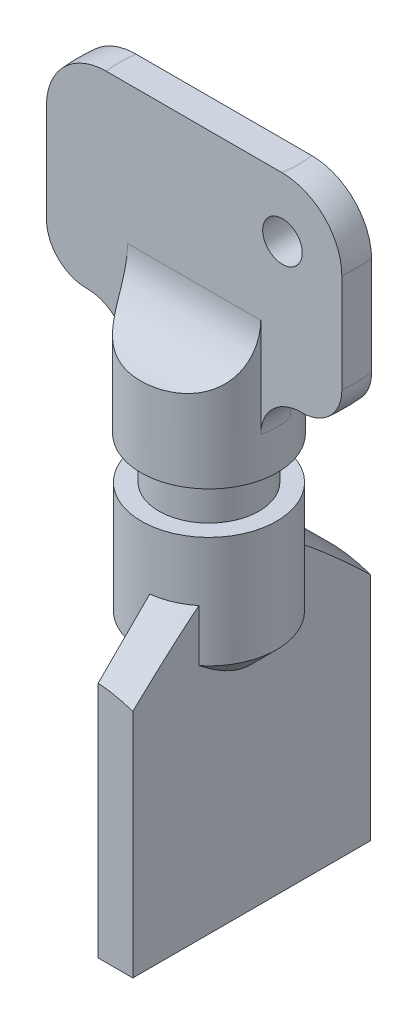
SolidWorks part; units mm, degrees
ref_plane "Front Plane" through (0, 0, 0) normal (0, 0, 1) x (1, 0, 0)
ref_plane "Top Plane" through (0, 0, 0) normal (0, 1, 0) x (1, 0, 0)
ref_plane "Right Plane" through (0, 0, 0) normal (1, 0, 0) x (0, 0, -1)
sketch "Sketch1" plane through (0, 0, 0) normal (0, 0, 1) x (1, 0, 0)
  line L0 (-3.4489, 37.7658) -> (-3.4489, 33.7658)
  line L1 (-3.4489, 33.7658) -> (-2.5348, 33.7658)
  line L2 (-2.5348, 33.7658) -> (-2.5348, 31.625)
  line L3 (-2.5348, 31.625) -> (-3.4177, 31.625)
  line L4 (-3.4177, 31.625) -> (-3.4177, 23)
  line L5 (-3.4177, 23) -> (0, 23)
  line L6 (-3.4489, 37.7658) -> (0, 37.7658)
  line L7 (0, 37.7658) -> (0, 23)
  dimension "D1" = 33.7658
  dimension "D2" = 2.1409
  dimension "D3" = 23
  dimension "D4" = 4
revolve "Revolve1" add sketch "Sketch1" angle 360 about L7
sketch "Sketch2" plane through (0, 37.7658, 0) normal (0, 1, 0) x (1, 0, 0)
  line L1 (-11.4046, 0.75) -> (11.4046, 0.75)
  line L2 (-11.4046, 0.75) -> (-11.4046, -0.75)
  line L3 (-11.4046, -0.75) -> (11.4046, -0.75)
  line L4 (11.4046, 0.75) -> (11.4046, -0.75)
  line L5 (-11.4046, 0.75) -> (11.4046, -0.75) construction
  line L6 (-11.4046, -0.75) -> (11.4046, 0.75) construction
  circle A0 centre (0, 0) radius 3.4489
  circle A1 centre (0, 0) radius 7.5
  circle M3 centre (0, 0) radius 3.4489
  dimension "D2" = 15
  dimension "D1" = 1.5
extrude "Boss-Extrude1" add sketch "Sketch2" along normal blind 10 contours L3 L1 M3 | L1 A1 L3 M3 | L3 A1 L1 M3 region at (-5.4544, 37.7658, 0) region at (0, 37.7658, 0) region at (5.4544, 37.7658, 0)
fillet "Fillet2" radius 2 4 edges at (7.5, 37.7658, 0) (-7.5, 37.7658, 0) (-3.4489, 37.7658, 0) (3.4489, 37.7658, 0)
fillet "Fillet3" radius 3 4 edges at (-7.5, 47.7658, 0) (7.5, 47.7658, 0) (0, 37.7658, -0.75) (0, 37.7658, 0.75)
sketch "Sketch3" plane through (0, 0, 0) normal (0, 0, 1) x (1, 0, 0)
  line L0 (-4.4371, 47.7658) -> (4.4371, 47.7658) construction
  line L1 (7.4624, 44.7658) -> (7.4624, 39.7658) construction
  circle A0 centre (4.4624, 44.7658) radius 1
  dimension "D1" = 2
  dimension "D2" = 3
  dimension "D3" = 3
extrude "Cut-Extrude1" cut sketch "Sketch3" against normal through all and the other way through all
sketch "Sketch4" plane through (0, 0, 0) normal (0, 0, 1) x (1, 0, 0)
  line L1 (0.4, 25.6253) -> (2.15, 25.6253)
  line L2 (0.4, 25.6253) -> (0.4, 14)
  line L3 (0.4, 14) -> (2.15, 14)
  line L4 (2.15, 25.6253) -> (2.15, 14)
  point P4 (4.2262, 13.6459)
  dimension "D1" = 2.15
  dimension "D2" = 0.4
  dimension "D3" = 14
  dimension "D4" = 1.75
extrude "Boss-Extrude2" add sketch "Sketch4" along normal blind 6 and the other way blind 6
chamfer "Chamfer1" distance 3 angle 45 2 edges at (1.3273, 25.6253, -3.1494) (1.3273, 25.6253, 3.1494)
chamfer "Chamfer2" distance 3 angle 45 2 edges at (3.4177, 23, 0) (-3.4177, 23, 0)
